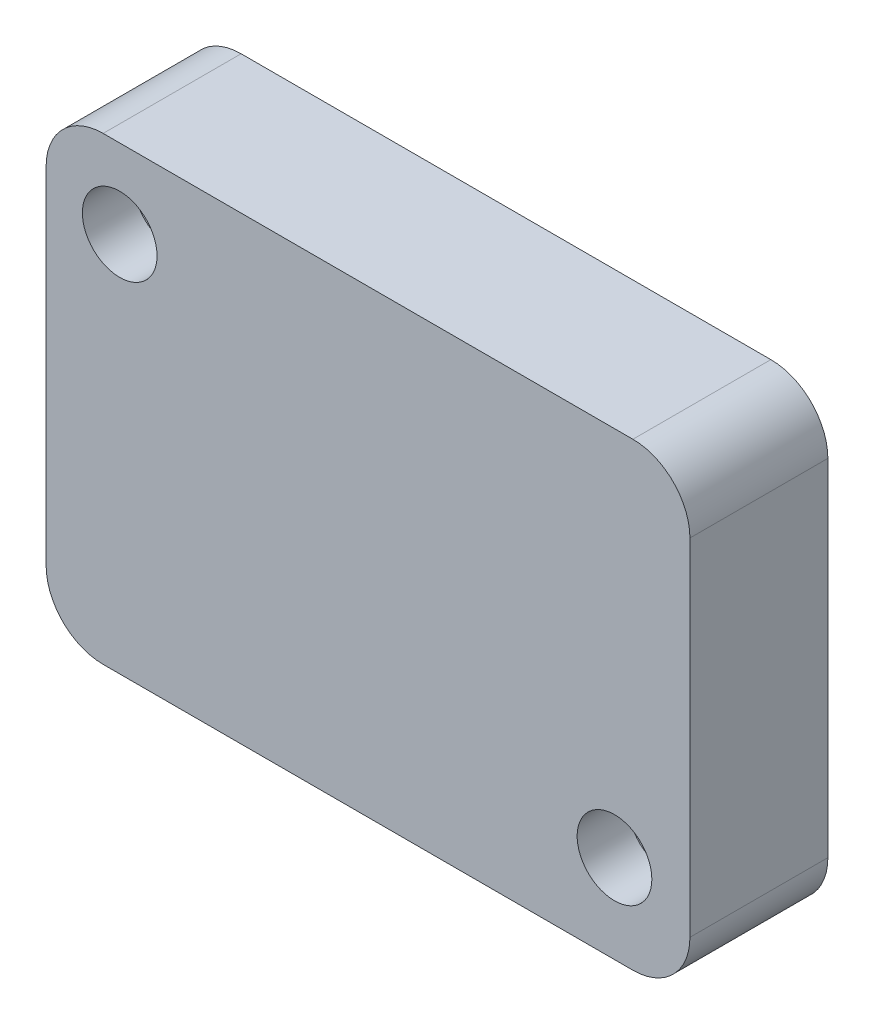
SolidWorks part; units mm, degrees
ref_plane "Top" through (0, 0, 0) normal (0, 0, 1) x (1, 0, 0)
ref_plane "Front_Back" through (0, 0, 0) normal (0, 1, 0) x (1, 0, 0)
ref_plane "Right_Left" through (0, 0, 0) normal (1, 0, 0) x (0, 0, -1)
sketch "Sketch1" plane through (0, 0, 0) normal (0, 0, 1) x (1, 0, 0)
  line L1 (-81.026, 63.5) -> (-7.874, 63.5)
  line L2 (-88.9, 55.626) -> (-88.9, 7.874)
  line L3 (-81.026, 0) -> (-7.874, 0)
  line L4 (0, 55.626) -> (0, 7.874)
  arc A0 (-81.026, 63.5) -> (-88.9, 55.626) centre (-81.026, 55.626) ccw
  arc A1 (-88.9, 7.874) -> (-81.026, 0) centre (-81.026, 7.874) ccw
  arc A2 (-7.874, 0) -> (0, 7.874) centre (-7.874, 7.874) ccw
  arc A3 (-7.874, 63.5) -> (0, 55.626) centre (-7.874, 55.626) cw
  point P6 (-88.9, 63.5)
  point P11 (0, 0)
  point P14 (0, 63.5)
  dimension "D3" = 7.874
  dimension "Depth" = 63.5
  dimension "Width" = 88.9
extrude "Die" add sketch "Sketch1" along normal blind 19.05
hole_wizard "Drill&CBore For 1/4 SHCS (Shallow)1" positions "Sketch3" profile "Sketch2" counterbore size "1/4" standard "MT&D Inch Mounting" end condition through all
sketch "Sketch3" plane through (0, 0, 19.05) normal (0, 0, 1) x (1, 0, 0)
  line L0 (-7.874, 63.5) -> (-81.026, 63.5) construction
  line L1 (-88.9, 55.626) -> (-88.9, 7.874) construction
  line L2 (0, 7.874) -> (0, 55.626) construction
  line L3 (-81.026, 0) -> (-7.874, 0) construction
  point P0 (-10.414, 12.192)
  point P1 (-78.74, 52.578)
  dimension "D1" = 10.922
  dimension "D2" = 10.16
  dimension "D3" = 10.414
  dimension "D4" = 12.192
sketch "Sketch2" plane through (-10.414, 12.192, 19.05) normal (1, 0, 0) x (0, -1, 0)
  line L0 (0, 0) -> (0, 19.05)
  line L1 (0, 19.05) -> (3.5687, 19.05)
  line L2 (4.318, 19.05) -> (-43.434, 19.05) construction
  line L3 (3.5687, 19.05) -> (3.5687, 7.112)
  line L4 (3.5687, 7.112) -> (5.1562, 7.112)
  line L5 (5.1562, 7.112) -> (5.1562, 0)
  line L7 (5.1562, 0) -> (0, 0)
  line L11 (0, -6.35) -> (0, 19.05) construction
  dimension "Thru Hole Dia." = 7.1374
  dimension "Thru Hole Depth" = 19.05
  dimension "C'Bore Dia." = 10.3124
  dimension "C'Bore Depth" = 7.112
